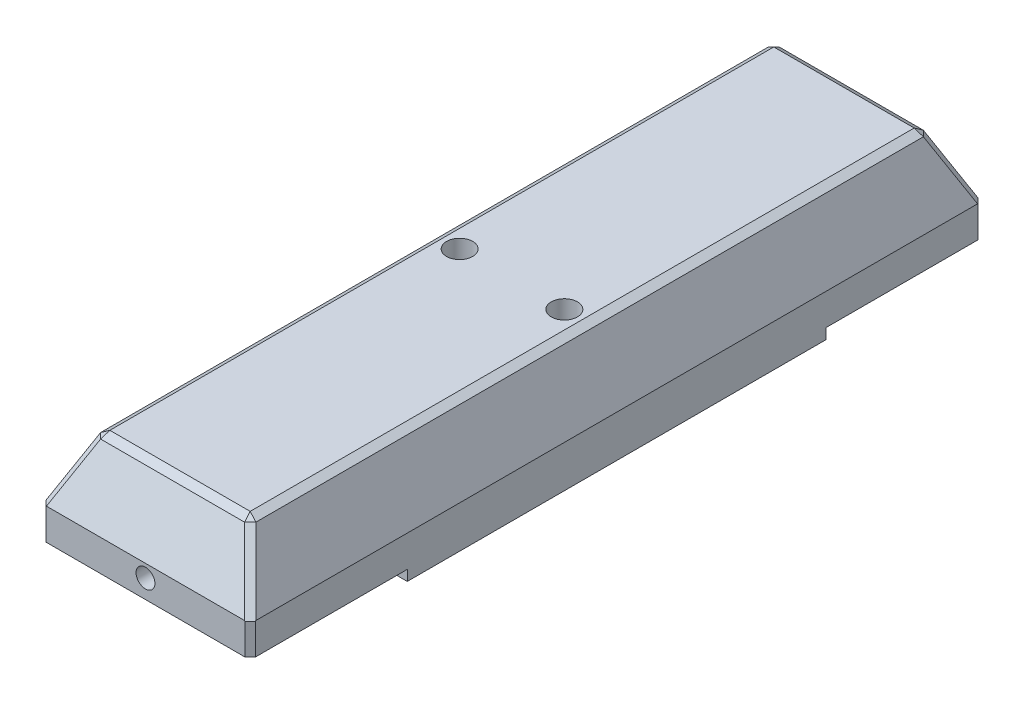
SolidWorks part; units mm, degrees
material "ABS"
ref_plane "正面" through (0, 0, 0) normal (0, 0, 1) x (1, 0, 0)
ref_plane "平面" through (0, 0, 0) normal (0, 1, 0) x (1, 0, 0)
ref_plane "右側面" through (0, 0, 0) normal (1, 0, 0) x (0, 0, -1)
sketch "ｽｹｯﾁ1" plane through (0, 0, 0) normal (0, 0, 1) x (1, 0, 0)
  line L3 (0, 0) -> (0, -4.2434) construction
  line L6 (-5, 0) -> (-5, -1.6451) construction
  line L7 (5, 0) -> (5, -1.6451) construction
  line L10 (-10, 0) -> (10, 0)
  line L12 (-10, 0) -> (-10, 3)
  line L13 (-10, 3) -> (-7.2022, 9)
  line L14 (-7.2022, 9) -> (7.2022, 9)
  line L15 (7.2022, 9) -> (10, 3)
  line L16 (10, 3) -> (10, 0)
  point P8 (0, 0)
  point P16 (-5, -0.7462)
  point P18 (5, -0.7462)
  dimension "D1" = 3
  dimension "D2" = 10
  dimension "D3" = 10
  dimension "D6" = 6
  dimension "D7" = 25
extrude "ﾎﾞｽ - 押し出し1" add sketch "ｽｹｯﾁ1" along normal blind 70
sketch "ｽｹｯﾁ2" plane through (10, 0, 0) normal (1, 0, 0) x (0, 0, -1)
  line L0 (-70, 3) -> (-67.2022, 9)
  line L1 (-70, 9) -> (0, 9) construction
  line L2 (-67.2022, 9) -> (-70, 9)
  line L3 (-70, 9) -> (-70, 3)
  line L4 (-35, 9) -> (-35, 0) construction
  line L6 (-2.7978, 9) -> (0, 9)
  line L7 (0, 3) -> (-2.7978, 9)
  line L8 (0, 9) -> (0, 3)
  line L9 (-70, 0) -> (0, 0) construction
  dimension "D1" = 25
extrude "ｶｯﾄ - 押し出し1" cut sketch "ｽｹｯﾁ2" against normal through all
chamfer "面取り1" distance 0.5 12 edges at (0, 9, 2.7978) (7.2022, 9, 35) (0, 9, 67.2022) (-7.2022, 9, 35) (10, 1.5, 70) (-10, 1.5, 70) (-10, 1.5, 0) (10, 1.5, 0) (8.6011, 6, 68.6011) (-8.6011, 6, 68.6011) (-8.6011, 6, 1.3989) (8.6011, 6, 1.3989)
sketch "ｽｹｯﾁ3" plane through (0, 0, 70) normal (0, 0, 1) x (1, 0, 0)
  line L0 (-9.5, 2.9541) -> (-9.5, 0) construction
  line L1 (9.1094, 0) -> (-9.5, 0)
  line L2 (9.1094, 0) -> (9.1094, 2.9541)
  line L3 (9.1094, 2.9541) -> (-9.5, 2.9541)
  line L4 (-9.5, 0) -> (-9.5, 2.9541)
  line L5 (9.1094, 0) -> (-9.5, 2.9541) construction
  line L6 (9.1094, 2.9541) -> (-9.5, 0) construction
  line L8 (-9.5, 0) -> (9.5, 0) construction
  point P0 (-0.1953, 1.477)
extrude "ﾎﾞｽ - 押し出し3" add sketch "ｽｹｯﾁ3" against normal blind 15.5
ref_plane "平面2" through (0, 0, 35) normal (0, 0, -1) x (-1, 0, 0)
sketch "ｽｹｯﾁ4" plane through (-10, 0, 0) normal (-1, 0, 0) x (0, 0, 1)
  line L0 (35, 1.65) -> (35, -1.65) construction
  line L1 (55, -1) -> (15, -1)
  line L2 (55, -1) -> (55, 0)
  line L3 (55, 0) -> (15, 0)
  line L4 (15, -1) -> (15, 0)
  line L5 (55, -1) -> (15, 0) construction
  line L6 (55, 0) -> (15, -1) construction
  line L7 (69.5, 0) -> (0.5, 0) construction
  point P0 (35, -0.5)
  point P9 (35, 0)
  dimension "D1" = 20
  dimension "D2" = 1
extrude "ﾎﾞｽ - 押し出し4" add sketch "ｽｹｯﾁ4" against normal up to surface (20 mm away) up to face at (10, 1.9847, 35)
sketch "ｽｹｯﾁ5" plane through (0, 0, 0) normal (0, 0, -1) x (-1, 0, 0)
  line L0 (0, 0) -> (0, 3) construction
  line L1 (9.4572, 3) -> (-9.4572, 3) construction
  line L2 (-10, -1) -> (10, -1) construction
  circle A0 centre (0, 1.78) radius 0.9
  dimension "D1" = 1.8
  dimension "D2" = 2.78
extrude "ｶｯﾄ - 押し出し2" cut sketch "ｽｹｯﾁ5" against normal through all
ref_axis "軸1" through (0, 1.78, 70) along (0, 0, -1)
ref_plane "平面3" through (0, 1.78, 0) normal (0, -1, 0) x (-1, 0, 0)
sketch "ｽｹｯﾁ6" plane through (0, 1.78, 0) normal (0, -1, 0) x (-1, 0, 0)
  line L0 (0, -70) -> (0, 0) construction
  line L1 (3.6, -63.75) -> (0, -63.75)
  line L2 (3.6, -63.75) -> (3.6, -60.25)
  line L3 (3.6, -60.25) -> (0, -60.25)
  line L4 (0, -63.75) -> (0, -60.25)
  line L5 (3.6, -63.75) -> (0, -60.25) construction
  line L6 (3.6, -60.25) -> (0, -63.75) construction
  line L7 (9.5, -70) -> (-9.5, -70) construction
  line L8 (1.65, -35) -> (-1.65, -35) construction
  line L9 (0, -6.25) -> (0, -9.75)
  line L10 (3.6, -9.75) -> (0, -9.75)
  line L11 (3.6, -6.25) -> (3.6, -9.75)
  line L12 (3.6, -6.25) -> (0, -6.25)
  point P0 (1.8, -62)
  dimension "D1" = 3.6
  dimension "D2" = 8
  dimension "D3" = 3.5
revolve "ｶｯﾄ - 回転1" cut sketch "ｽｹｯﾁ6" angle 360 about axis through (0, 1.78, 70) along (0, 0, -1)
sketch "ｽｹｯﾁ7" plane through (0, 9, 0) normal (0, 1, 0) x (1, 0, 0)
  line L0 (-10, -35) -> (10, -35) construction
  line L1 (-10, -69.4572) -> (-10, -0.5428) construction
  line L2 (10, -69.4572) -> (10, -0.5428) construction
  circle A0 centre (-5, -35) radius 1.25
  circle A1 centre (5, -35) radius 1.25
  point P10 (0, -35)
  dimension "D1" = 2.5
  dimension "D2" = 10
  dimension "D3" = 5
extrude "ｶｯﾄ - 押し出し3" cut sketch "ｽｹｯﾁ7" against normal through all
